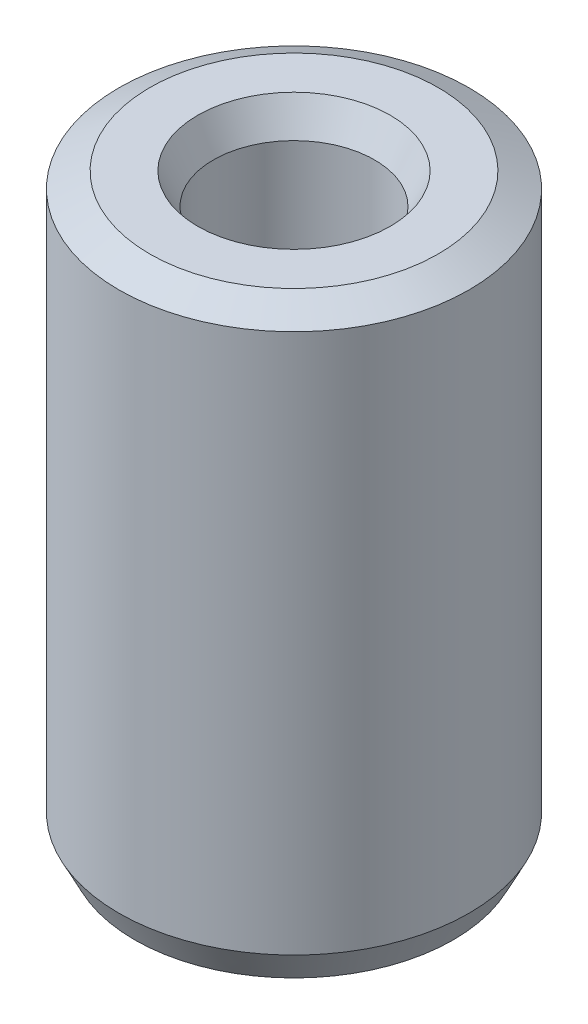
SolidWorks part; units mm, degrees
ref_plane "Front Plane" through (0, 0, 0) normal (0, 0, 1) x (1, 0, 0)
ref_plane "Top Plane" through (0, 0, 0) normal (0, 1, 0) x (1, 0, 0)
ref_plane "Right Plane" through (0, 0, 0) normal (1, 0, 0) x (0, 0, -1)
sketch "Sketch1" plane through (0, 0, 0) normal (0, 1, 0) x (1, 0, 0)
  circle A0 centre (0, 0) radius 5
  dimension "SLEEVE_OD" = 10
extrude "Boss-Extrude1" add sketch "Sketch1" along normal blind 16.7458
sketch "Sketch2" plane through (0, 0, 0) normal (0, 1, 0) x (1, 0, 0)
  circle A0 centre (0, 0) radius 2.3033
  dimension "BORE_D" = 4.6066
extrude "Cut-Extrude1" cut sketch "Sketch2" along normal through all
chamfer "Chamfer1" distance 0.4462 angle 63.154 4 edges at (0, 16.7458, 2.3033) (0, 0, 2.3033) (0, 0, 5) (0, 16.7458, 5) first distance on face at (0, 16.7458, 2.3033) first distance on face at (0, 0, 2.3033) first distance on face at (0, 16.7458, 5)
